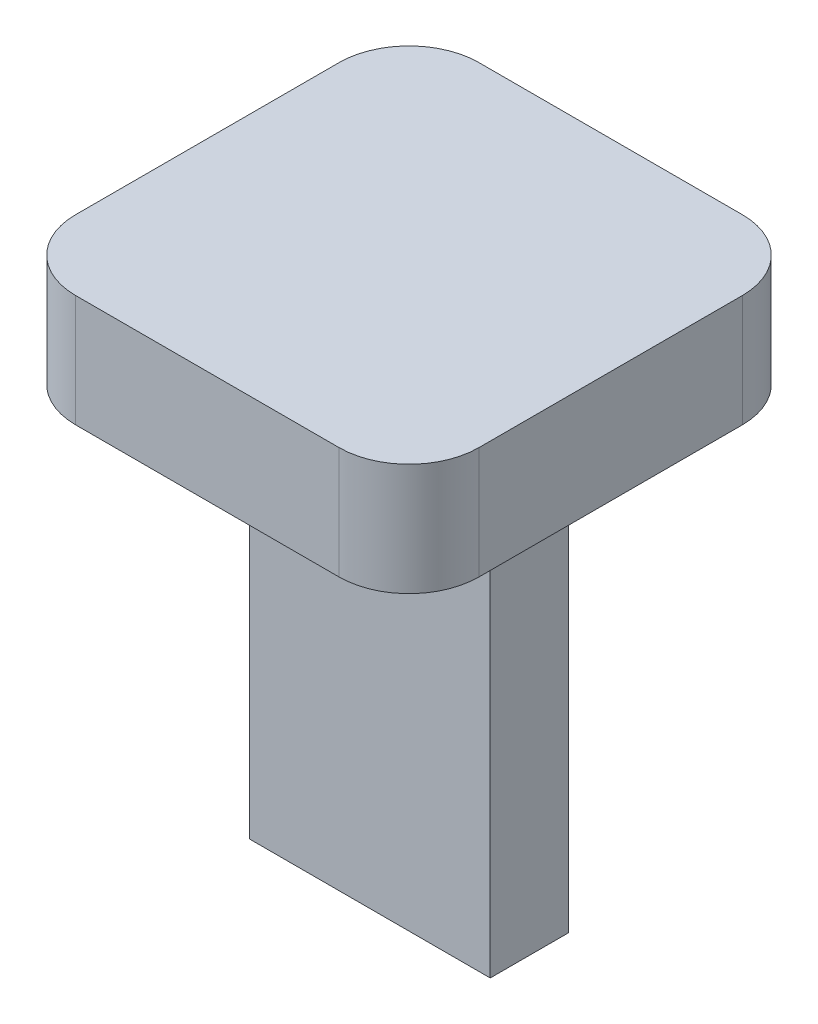
SolidWorks part; units mm, degrees
ref_plane "Front Plane" through (0, 0, 0) normal (0, 0, 1) x (1, 0, 0)
ref_plane "Top Plane" through (0, 0, 0) normal (0, 1, 0) x (1, 0, 0)
ref_plane "Right Plane" through (0, 0, 0) normal (1, 0, 0) x (0, 0, -1)
sketch "Sketch1" plane through (0, 0, 0) normal (0, 1, 0) x (1, 0, 0)
  line L1 (-2.15, 0.7) -> (2.15, 0.7)
  line L2 (-2.15, 0.7) -> (-2.15, -0.7)
  line L3 (-2.15, -0.7) -> (2.15, -0.7)
  line L4 (2.15, 0.7) -> (2.15, -0.7)
  line L5 (0, -0.7) -> (0, 0.7) construction
  line L6 (-2.15, 0) -> (2.15, 0) construction
  point P0 (0, 0)
  dimension "D1" = 1.4
  dimension "D2" = 4.3
extrude "Boss-Extrude1" add sketch "Sketch1" along normal blind 7.75
sketch "Sketch2" plane through (0, 7.75, 0) normal (0, 1, 0) x (1, 0, 0)
  line L1 (-3.6, 3.6) -> (3.6, 3.6)
  line L2 (-3.6, 3.6) -> (-3.6, -3.6)
  line L3 (-3.6, -3.6) -> (3.6, -3.6)
  line L4 (3.6, 3.6) -> (3.6, -3.6)
  line L5 (0, -3.6) -> (0, 3.6) construction
  line L6 (-3.6, 0) -> (3.6, 0) construction
  point P0 (0, 0)
  dimension "D1" = 7.2
  dimension "D2" = 7.2
extrude "Boss-Extrude2" add sketch "Sketch2" along normal blind 2
fillet "Fillet1" radius 1.25 8 edges at (2.15, 7.75, 0) (0, 7.75, -0.7) (-2.15, 7.75, 0) (0, 7.75, 0.7) (3.6, 8.75, -3.6) (3.6, 8.75, 3.6) (-3.6, 8.75, 3.6) (-3.6, 8.75, -3.6)
